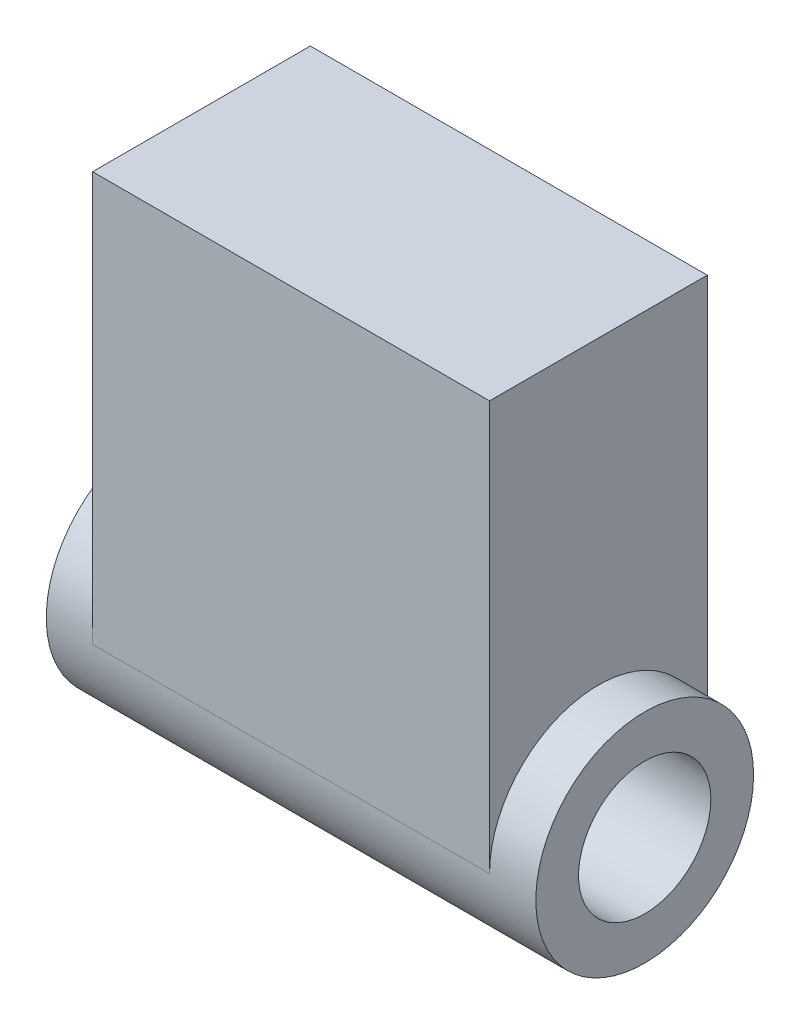
SolidWorks part; units mm, degrees
ref_plane "정면" through (0, 0, 0) normal (0, 0, 1) x (1, 0, 0)
ref_plane "윗면" through (0, 0, 0) normal (0, 1, 0) x (1, 0, 0)
ref_plane "우측면" through (0, 0, 0) normal (1, 0, 0) x (0, 0, -1)
sketch "스케치1" plane through (0, 0, 0) normal (1, 0, 0) x (0, 0, -1)
  line L0 (-3.2914, 0) -> (-3.2914, 12.3765)
  line L1 (-3.2914, 12.3765) -> (3.2914, 12.3765)
  line L2 (3.2914, 12.3765) -> (3.2914, 0)
  circle A0 centre (0, 0) radius 3.2914
  circle A1 centre (0, 0) radius 2
  dimension "D1" = 4
extrude "보스-돌출1" add sketch "스케치1" along normal mid plane 14.8 contours A0 A1 region at (0, 3.1983, 0)
extrude "보스-돌출2" add sketch "스케치1<3>" along normal mid plane 12 contours A0 L2 L1 L0 region at (0, 7.4532, 0)
sketch "스케치1<3>" plane through (0, 0, 0) normal (1, 0, 0) x (0, 0, -1) same geometry as "스케치1"
